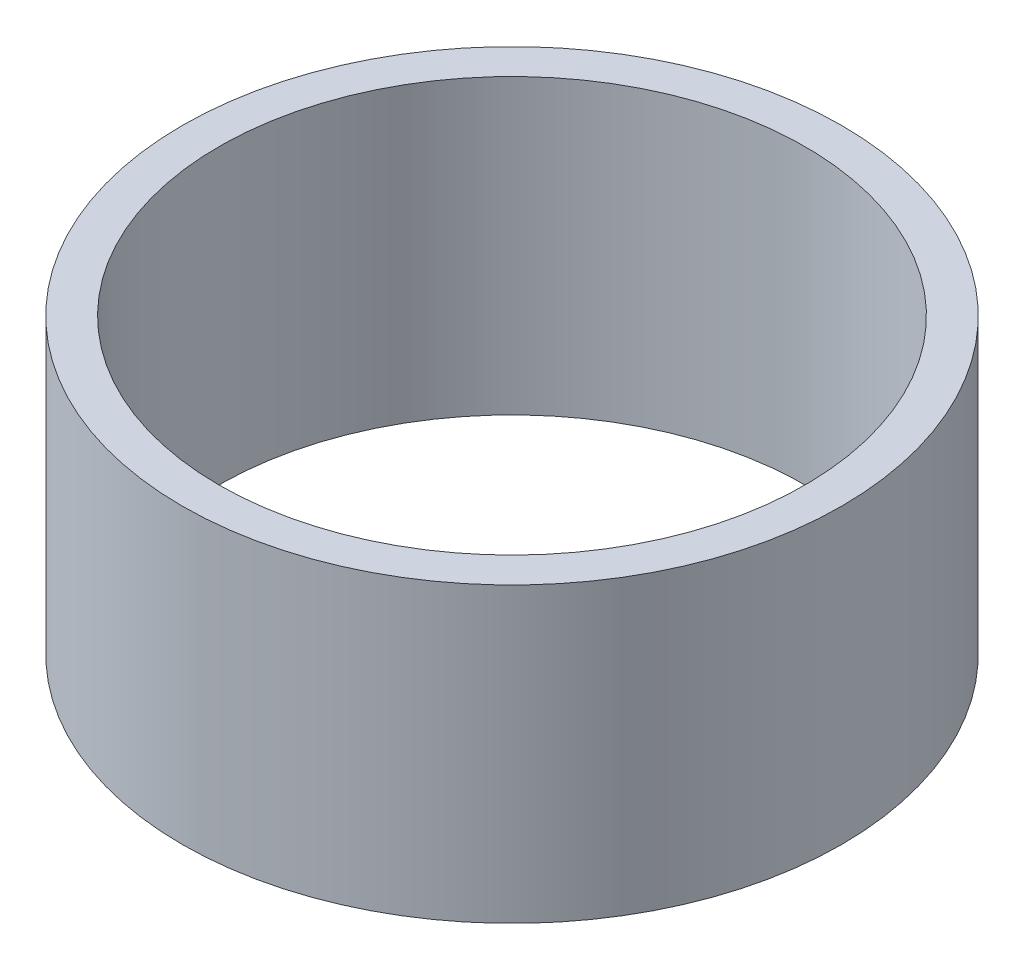
SolidWorks part; units mm, degrees
ref_plane "Front Plane" through (0, 0, 0) normal (0, 0, 1) x (1, 0, 0)
ref_plane "Top Plane" through (0, 0, 0) normal (0, 1, 0) x (1, 0, 0)
ref_plane "Right Plane" through (0, 0, 0) normal (1, 0, 0) x (0, 0, -1)
sketch "Sketch1" plane through (0, 0, 0) normal (0, 1, 0) x (1, 0, 0)
  circle A0 centre (0, 0) radius 20
  circle A1 centre (0, 0) radius 22.5
  dimension "D1" = 40
  dimension "D2" = 45
extrude "Boss-Extrude1" add sketch "Sketch1" along normal blind 20
